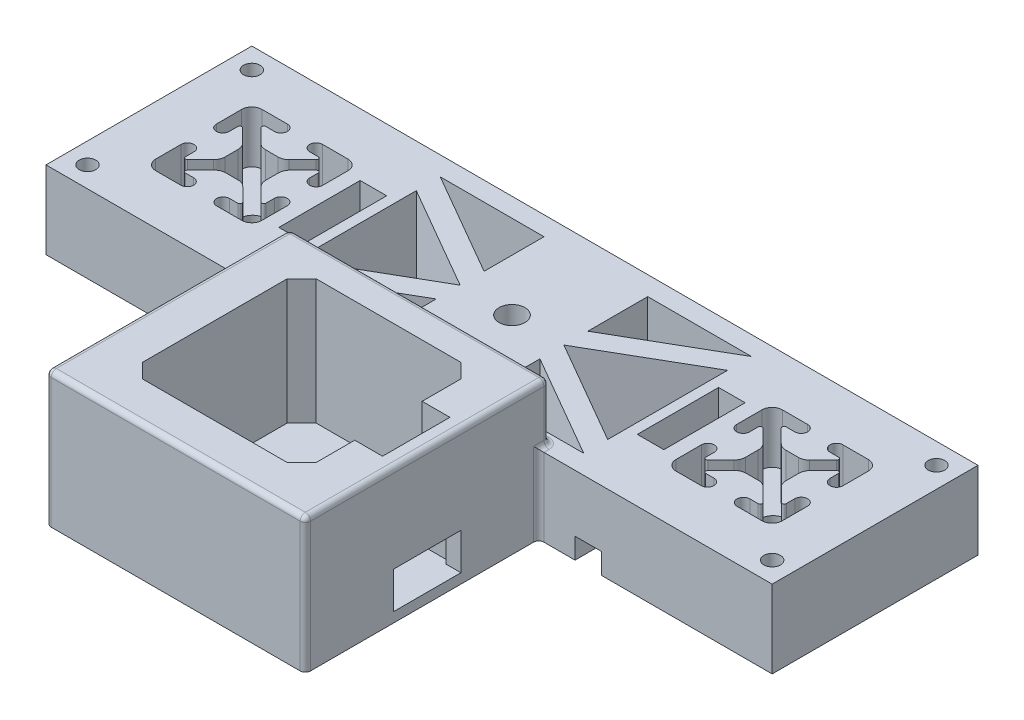
SolidWorks part; units mm, degrees
ref_plane "Front" through (0, 0, 0) normal (0, 0, 1) x (1, 0, 0)
ref_plane "Top" through (0, 0, 0) normal (0, 1, 0) x (1, 0, 0)
ref_plane "Right" through (0, 0, 0) normal (1, 0, 0) x (0, 0, -1)
sketch "Sketch1" plane through (0, 0, 0) normal (0, 1, 0) x (1, 0, 0)
  line L1 (0, 0) -> (177.8, 0)
  line L2 (0, 0) -> (0, 50.4)
  line L3 (0, 50.4) -> (177.8, 50.4)
  line L4 (177.8, 0) -> (177.8, 50.4)
  dimension "D1" = 177.8
  dimension "D2" = 50.4
extrude "Boss-Extrude1" add sketch "Sketch1" along normal blind 6.35
sketch "Sketch2" plane through (0, 6.35, 0) normal (0, 1, 0) x (1, 0, 0)
  line L0 (37.6996, 29.52) -> (37.6996, 35.7372) construction
  line L1 (35.7368, 37.7) -> (29.5196, 37.7) construction
  line L2 (29.5196, 35.56) -> (31.619, 35.56) construction
  line L3 (32.3326, 33.8353) -> (28.9966, 30.504) construction
  line L4 (26.7566, 29.5771) -> (23.643, 29.5771) construction
  line L5 (21.403, 30.504) -> (18.067, 33.8353) construction
  line L6 (18.7806, 35.56) -> (20.88, 35.56) construction
  line L7 (20.88, 37.7) -> (14.6628, 37.7) construction
  line L8 (12.7, 35.7372) -> (12.7, 29.52) construction
  line L9 (14.84, 29.52) -> (14.84, 31.5965) construction
  line L10 (16.5637, 32.3112) -> (19.7659, 29.1135) construction
  line L11 (20.743, 26.7568) -> (20.743, 23.6432) construction
  line L12 (19.7659, 21.2865) -> (16.5637, 18.0888) construction
  line L13 (14.84, 18.8035) -> (14.84, 20.88) construction
  line L14 (12.7, 20.88) -> (12.7, 14.6628) construction
  line L15 (14.6628, 12.7) -> (20.8121, 12.7) construction
  line L16 (20.8121, 14.84) -> (18.7806, 14.84) construction
  line L17 (18.067, 16.5647) -> (21.403, 19.896) construction
  line L18 (23.643, 20.8229) -> (26.7566, 20.8229) construction
  line L19 (28.9966, 19.896) -> (32.3326, 16.5647) construction
  line L20 (31.619, 14.84) -> (29.5875, 14.84) construction
  line L21 (29.5875, 12.7) -> (35.7368, 12.7) construction
  line L22 (37.6996, 14.6628) -> (37.6996, 20.88) construction
  line L23 (35.5596, 20.88) -> (35.5596, 18.8035) construction
  line L24 (33.8359, 18.0888) -> (30.6337, 21.2865) construction
  line L25 (29.6566, 23.6432) -> (29.6566, 26.7568) construction
  line L26 (30.6337, 29.1135) -> (33.8359, 32.3112) construction
  line L27 (35.5596, 31.5965) -> (35.5596, 29.52) construction
  line L28 (0, 50.4) -> (0, 0) construction
  line L29 (177.8, 50.4) -> (0, 50.4) construction
  line L30 (0, 0) -> (177.8, 0) construction
  line L31 (88.9, 50.4) -> (88.9, 0) construction
  line L32 (142.2404, 31.5965) -> (142.2404, 29.52) construction
  line L33 (147.1663, 29.1135) -> (143.9641, 32.3112) construction
  line L34 (148.1434, 23.6432) -> (148.1434, 26.7568) construction
  line L35 (143.9641, 18.0888) -> (147.1663, 21.2865) construction
  line L36 (142.2404, 20.88) -> (142.2404, 18.8035) construction
  line L37 (140.1004, 14.6628) -> (140.1004, 20.88) construction
  line L38 (148.2125, 12.7) -> (142.0632, 12.7) construction
  line L39 (146.181, 14.84) -> (148.2125, 14.84) construction
  line L40 (148.8034, 19.896) -> (145.4674, 16.5647) construction
  line L41 (154.157, 20.8229) -> (151.0434, 20.8229) construction
  line L42 (159.733, 16.5647) -> (156.397, 19.896) construction
  line L43 (156.9879, 14.84) -> (159.0194, 14.84) construction
  line L44 (163.1372, 12.7) -> (156.9879, 12.7) construction
  line L45 (165.1, 20.88) -> (165.1, 14.6628) construction
  line L46 (162.96, 18.8035) -> (162.96, 20.88) construction
  line L47 (158.0341, 21.2865) -> (161.2363, 18.0888) construction
  line L48 (157.057, 26.7568) -> (157.057, 23.6432) construction
  line L49 (161.2363, 32.3112) -> (158.0341, 29.1135) construction
  line L50 (162.96, 29.52) -> (162.96, 31.5965) construction
  line L51 (165.1, 35.7372) -> (165.1, 29.52) construction
  line L52 (156.92, 37.7) -> (163.1372, 37.7) construction
  line L53 (159.0194, 35.56) -> (156.92, 35.56) construction
  line L54 (156.397, 30.504) -> (159.733, 33.8353) construction
  line L55 (151.0434, 29.5771) -> (154.157, 29.5771) construction
  line L56 (145.4674, 33.8353) -> (148.8034, 30.504) construction
  line L57 (148.2804, 35.56) -> (146.181, 35.56) construction
  line L58 (142.0632, 37.7) -> (148.2804, 37.7) construction
  line L59 (140.1004, 29.52) -> (140.1004, 35.7372) construction
  line L60 (38.2076, 29.52) -> (38.2076, 35.7372)
  line L62 (0, 50.4) -> (0, 0)
  line L63 (0, 0) -> (177.8, 0)
  line L64 (177.8, 50.4) -> (177.8, 0)
  line L65 (35.7368, 38.208) -> (29.5196, 38.208)
  line L66 (29.5196, 35.052) -> (31.619, 35.052)
  line L67 (31.9737, 34.1948) -> (28.6376, 30.8635)
  line L68 (26.7566, 30.0851) -> (23.643, 30.0851)
  line L69 (21.762, 30.8635) -> (18.4259, 34.1948)
  line L70 (18.7806, 35.052) -> (20.88, 35.052)
  line L71 (20.88, 38.208) -> (14.6628, 38.208)
  line L72 (12.192, 35.7372) -> (12.192, 29.52)
  line L73 (15.348, 29.52) -> (15.348, 31.5965)
  line L74 (16.2047, 31.9517) -> (19.4069, 28.7541)
  line L75 (20.235, 26.7568) -> (20.235, 23.6432)
  line L76 (19.4069, 21.6459) -> (16.2047, 18.4483)
  line L77 (15.348, 18.8035) -> (15.348, 20.88)
  line L78 (12.192, 20.88) -> (12.192, 14.6628)
  line L79 (14.6628, 12.192) -> (20.8121, 12.192)
  line L80 (20.8121, 15.348) -> (18.7806, 15.348)
  line L81 (18.4259, 16.2052) -> (21.762, 19.5365)
  line L82 (23.643, 20.3149) -> (26.7566, 20.3149)
  line L83 (28.6376, 19.5365) -> (31.9737, 16.2052)
  line L84 (31.619, 15.348) -> (29.5875, 15.348)
  line L85 (29.5875, 12.192) -> (35.7368, 12.192)
  line L86 (38.2076, 14.6628) -> (38.2076, 20.88)
  line L87 (35.0516, 20.88) -> (35.0516, 18.8035)
  line L88 (34.1949, 18.4483) -> (30.9927, 21.6459)
  line L89 (30.1646, 23.6432) -> (30.1646, 26.7568)
  line L90 (30.9927, 28.7541) -> (34.1949, 31.9517)
  line L91 (35.0516, 31.5965) -> (35.0516, 29.52)
  line L92 (142.7484, 31.5965) -> (142.7484, 29.52)
  line L93 (139.5924, 29.52) -> (139.5924, 35.7372)
  line L94 (142.0632, 38.208) -> (148.2804, 38.208)
  line L95 (148.2804, 35.052) -> (146.181, 35.052)
  line L96 (145.8263, 34.1948) -> (149.1624, 30.8635)
  line L97 (151.0434, 30.0851) -> (154.157, 30.0851)
  line L98 (156.038, 30.8635) -> (159.3741, 34.1948)
  line L99 (159.0194, 35.052) -> (156.92, 35.052)
  line L100 (156.92, 38.208) -> (163.1372, 38.208)
  line L101 (165.608, 35.7372) -> (165.608, 29.52)
  line L102 (162.452, 29.52) -> (162.452, 31.5965)
  line L103 (161.5953, 31.9517) -> (158.3931, 28.7541)
  line L104 (157.565, 26.7568) -> (157.565, 23.6432)
  line L105 (158.3931, 21.6459) -> (161.5953, 18.4483)
  line L106 (162.452, 18.8035) -> (162.452, 20.88)
  line L107 (165.608, 20.88) -> (165.608, 14.6628)
  line L108 (163.1372, 12.192) -> (156.9879, 12.192)
  line L109 (156.9879, 15.348) -> (159.0194, 15.348)
  line L110 (159.3741, 16.2052) -> (156.038, 19.5365)
  line L111 (154.157, 20.3149) -> (151.0434, 20.3149)
  line L112 (149.1624, 19.5365) -> (145.8263, 16.2052)
  line L113 (146.181, 15.348) -> (148.2125, 15.348)
  line L114 (148.2125, 12.192) -> (142.0632, 12.192)
  line L115 (139.5924, 14.6628) -> (139.5924, 20.88)
  line L116 (142.7484, 20.88) -> (142.7484, 18.8035)
  line L117 (143.6051, 18.4483) -> (146.8073, 21.6459)
  line L118 (147.6354, 23.6432) -> (147.6354, 26.7568)
  line L119 (146.8073, 28.7541) -> (143.6051, 31.9517)
  line L120 (177.8, 50.4) -> (0, 50.4)
  arc A1 (37.6996, 35.7372) -> (35.7368, 37.7) centre (35.7368, 35.7372) ccw construction
  arc A2 (29.5196, 37.7) -> (29.5196, 35.56) centre (29.5196, 36.63) ccw construction
  arc A3 (31.619, 35.56) -> (32.3326, 33.8353) centre (31.619, 34.55) cw construction
  arc A4 (28.9966, 30.504) -> (26.7566, 29.5771) centre (26.7566, 32.7471) cw construction
  arc A5 (23.643, 29.5771) -> (21.403, 30.504) centre (23.643, 32.7471) cw construction
  arc A6 (18.067, 33.8353) -> (18.7806, 35.56) centre (18.7806, 34.55) cw construction
  arc A7 (20.88, 35.56) -> (20.88, 37.7) centre (20.88, 36.63) ccw construction
  arc A8 (14.6628, 37.7) -> (12.7, 35.7372) centre (14.6628, 35.7372) ccw construction
  arc A9 (12.7, 29.52) -> (14.84, 29.52) centre (13.77, 29.52) ccw construction
  arc A10 (14.84, 31.5965) -> (16.5637, 32.3112) centre (15.85, 31.5965) cw construction
  arc A11 (19.7659, 29.1135) -> (20.743, 26.7568) centre (17.4126, 26.7568) cw construction
  arc A12 (20.743, 23.6432) -> (19.7659, 21.2865) centre (17.4126, 23.6432) cw construction
  arc A13 (16.5637, 18.0888) -> (14.84, 18.8035) centre (15.85, 18.8035) cw construction
  arc A14 (14.84, 20.88) -> (12.7, 20.88) centre (13.77, 20.88) ccw construction
  arc A15 (12.7, 14.6628) -> (14.6628, 12.7) centre (14.6628, 14.6628) ccw construction
  arc A16 (20.8121, 12.7) -> (20.8121, 14.84) centre (20.8121, 13.77) ccw construction
  arc A17 (18.7806, 14.84) -> (18.067, 16.5647) centre (18.7806, 15.85) cw construction
  arc A18 (21.403, 19.896) -> (23.643, 20.8229) centre (23.643, 17.6529) cw construction
  arc A19 (26.7566, 20.8229) -> (28.9966, 19.896) centre (26.7566, 17.6529) cw construction
  arc A20 (32.3326, 16.5647) -> (31.619, 14.84) centre (31.619, 15.85) cw construction
  arc A21 (29.5875, 14.84) -> (29.5875, 12.7) centre (29.5875, 13.77) ccw construction
  arc A22 (35.7368, 12.7) -> (37.6996, 14.6628) centre (35.7368, 14.6628) ccw construction
  arc A23 (37.6996, 20.88) -> (35.5596, 20.88) centre (36.6296, 20.88) ccw construction
  arc A24 (35.5596, 18.8035) -> (33.8359, 18.0888) centre (34.5496, 18.8035) cw construction
  arc A25 (30.6337, 21.2865) -> (29.6566, 23.6432) centre (32.987, 23.6432) cw construction
  arc A26 (29.6566, 26.7568) -> (30.6337, 29.1135) centre (32.987, 26.7568) cw construction
  arc A27 (33.8359, 32.3112) -> (35.5596, 31.5965) centre (34.5496, 31.5965) cw construction
  arc A28 (35.5596, 29.52) -> (37.6996, 29.52) centre (36.6296, 29.52) ccw construction
  arc A29 (142.2404, 29.52) -> (140.1004, 29.52) centre (141.1704, 29.52) cw construction
  arc A30 (143.9641, 32.3112) -> (142.2404, 31.5965) centre (143.2504, 31.5965) ccw construction
  arc A31 (148.1434, 26.7568) -> (147.1663, 29.1135) centre (144.813, 26.7568) ccw construction
  arc A32 (147.1663, 21.2865) -> (148.1434, 23.6432) centre (144.813, 23.6432) ccw construction
  arc A33 (142.2404, 18.8035) -> (143.9641, 18.0888) centre (143.2504, 18.8035) ccw construction
  arc A34 (140.1004, 20.88) -> (142.2404, 20.88) centre (141.1704, 20.88) cw construction
  arc A35 (142.0632, 12.7) -> (140.1004, 14.6628) centre (142.0632, 14.6628) cw construction
  arc A36 (148.2125, 14.84) -> (148.2125, 12.7) centre (148.2125, 13.77) cw construction
  arc A37 (145.4674, 16.5647) -> (146.181, 14.84) centre (146.181, 15.85) ccw construction
  arc A38 (151.0434, 20.8229) -> (148.8034, 19.896) centre (151.0434, 17.6529) ccw construction
  arc A39 (156.397, 19.896) -> (154.157, 20.8229) centre (154.157, 17.6529) ccw construction
  arc A40 (159.0194, 14.84) -> (159.733, 16.5647) centre (159.0194, 15.85) ccw construction
  arc A41 (156.9879, 12.7) -> (156.9879, 14.84) centre (156.9879, 13.77) cw construction
  arc A42 (165.1, 14.6628) -> (163.1372, 12.7) centre (163.1372, 14.6628) cw construction
  arc A43 (162.96, 20.88) -> (165.1, 20.88) centre (164.03, 20.88) cw construction
  arc A44 (161.2363, 18.0888) -> (162.96, 18.8035) centre (161.95, 18.8035) ccw construction
  arc A45 (157.057, 23.6432) -> (158.0341, 21.2865) centre (160.3874, 23.6432) ccw construction
  arc A46 (158.0341, 29.1135) -> (157.057, 26.7568) centre (160.3874, 26.7568) ccw construction
  arc A47 (162.96, 31.5965) -> (161.2363, 32.3112) centre (161.95, 31.5965) ccw construction
  arc A48 (165.1, 29.52) -> (162.96, 29.52) centre (164.03, 29.52) cw construction
  arc A49 (163.1372, 37.7) -> (165.1, 35.7372) centre (163.1372, 35.7372) cw construction
  arc A50 (156.92, 35.56) -> (156.92, 37.7) centre (156.92, 36.63) cw construction
  arc A51 (159.733, 33.8353) -> (159.0194, 35.56) centre (159.0194, 34.55) ccw construction
  arc A52 (154.157, 29.5771) -> (156.397, 30.504) centre (154.157, 32.7471) ccw construction
  arc A53 (148.8034, 30.504) -> (151.0434, 29.5771) centre (151.0434, 32.7471) ccw construction
  arc A54 (146.181, 35.56) -> (145.4674, 33.8353) centre (146.181, 34.55) ccw construction
  arc A55 (148.2804, 37.7) -> (148.2804, 35.56) centre (148.2804, 36.63) cw construction
  arc A56 (140.1004, 35.7372) -> (142.0632, 37.7) centre (142.0632, 35.7372) cw construction
  arc A58 (38.2076, 35.7372) -> (35.7368, 38.208) centre (35.7368, 35.7372) ccw
  arc A59 (29.5196, 38.208) -> (29.5196, 35.052) centre (29.5196, 36.63) ccw
  arc A60 (31.619, 35.052) -> (31.9737, 34.1948) centre (31.619, 34.55) cw
  arc A61 (28.6376, 30.8635) -> (26.7566, 30.0851) centre (26.7566, 32.7471) cw
  arc A62 (23.643, 30.0851) -> (21.762, 30.8635) centre (23.643, 32.7471) cw
  arc A63 (18.4259, 34.1948) -> (18.7806, 35.052) centre (18.7806, 34.55) cw
  arc A64 (20.88, 35.052) -> (20.88, 38.208) centre (20.88, 36.63) ccw
  arc A65 (14.6628, 38.208) -> (12.192, 35.7372) centre (14.6628, 35.7372) ccw
  arc A66 (12.192, 29.52) -> (15.348, 29.52) centre (13.77, 29.52) ccw
  arc A67 (15.348, 31.5965) -> (16.2047, 31.9517) centre (15.85, 31.5965) cw
  arc A68 (19.4069, 28.7541) -> (20.235, 26.7568) centre (17.4126, 26.7568) cw
  arc A69 (20.235, 23.6432) -> (19.4069, 21.6459) centre (17.4126, 23.6432) cw
  arc A70 (16.2047, 18.4483) -> (15.348, 18.8035) centre (15.85, 18.8035) cw
  arc A71 (15.348, 20.88) -> (12.192, 20.88) centre (13.77, 20.88) ccw
  arc A72 (12.192, 14.6628) -> (14.6628, 12.192) centre (14.6628, 14.6628) ccw
  arc A73 (20.8121, 12.192) -> (20.8121, 15.348) centre (20.8121, 13.77) ccw
  arc A74 (18.7806, 15.348) -> (18.4259, 16.2052) centre (18.7806, 15.85) cw
  arc A75 (21.762, 19.5365) -> (23.643, 20.3149) centre (23.643, 17.6529) cw
  arc A76 (26.7566, 20.3149) -> (28.6376, 19.5365) centre (26.7566, 17.6529) cw
  arc A77 (31.9737, 16.2052) -> (31.619, 15.348) centre (31.619, 15.85) cw
  arc A78 (29.5875, 15.348) -> (29.5875, 12.192) centre (29.5875, 13.77) ccw
  arc A79 (35.7368, 12.192) -> (38.2076, 14.6628) centre (35.7368, 14.6628) ccw
  arc A80 (38.2076, 20.88) -> (35.0516, 20.88) centre (36.6296, 20.88) ccw
  arc A81 (35.0516, 18.8035) -> (34.1949, 18.4483) centre (34.5496, 18.8035) cw
  arc A82 (30.9927, 21.6459) -> (30.1646, 23.6432) centre (32.987, 23.6432) cw
  arc A83 (30.1646, 26.7568) -> (30.9927, 28.7541) centre (32.987, 26.7568) cw
  arc A84 (34.1949, 31.9517) -> (35.0516, 31.5965) centre (34.5496, 31.5965) cw
  arc A85 (35.0516, 29.52) -> (38.2076, 29.52) centre (36.6296, 29.52) ccw
  arc A86 (142.7484, 29.52) -> (139.5924, 29.52) centre (141.1704, 29.52) cw
  arc A87 (139.5924, 35.7372) -> (142.0632, 38.208) centre (142.0632, 35.7372) cw
  arc A88 (148.2804, 38.208) -> (148.2804, 35.052) centre (148.2804, 36.63) cw
  arc A89 (146.181, 35.052) -> (145.8263, 34.1948) centre (146.181, 34.55) ccw
  arc A90 (149.1624, 30.8635) -> (151.0434, 30.0851) centre (151.0434, 32.7471) ccw
  arc A91 (154.157, 30.0851) -> (156.038, 30.8635) centre (154.157, 32.7471) ccw
  arc A92 (159.3741, 34.1948) -> (159.0194, 35.052) centre (159.0194, 34.55) ccw
  arc A93 (156.92, 35.052) -> (156.92, 38.208) centre (156.92, 36.63) cw
  arc A94 (163.1372, 38.208) -> (165.608, 35.7372) centre (163.1372, 35.7372) cw
  arc A95 (165.608, 29.52) -> (162.452, 29.52) centre (164.03, 29.52) cw
  arc A96 (162.452, 31.5965) -> (161.5953, 31.9517) centre (161.95, 31.5965) ccw
  arc A97 (158.3931, 28.7541) -> (157.565, 26.7568) centre (160.3874, 26.7568) ccw
  arc A98 (157.565, 23.6432) -> (158.3931, 21.6459) centre (160.3874, 23.6432) ccw
  arc A99 (161.5953, 18.4483) -> (162.452, 18.8035) centre (161.95, 18.8035) ccw
  arc A100 (162.452, 20.88) -> (165.608, 20.88) centre (164.03, 20.88) cw
  arc A101 (165.608, 14.6628) -> (163.1372, 12.192) centre (163.1372, 14.6628) cw
  arc A102 (156.9879, 12.192) -> (156.9879, 15.348) centre (156.9879, 13.77) cw
  arc A103 (159.0194, 15.348) -> (159.3741, 16.2052) centre (159.0194, 15.85) ccw
  arc A104 (156.038, 19.5365) -> (154.157, 20.3149) centre (154.157, 17.6529) ccw
  arc A105 (151.0434, 20.3149) -> (149.1624, 19.5365) centre (151.0434, 17.6529) ccw
  arc A106 (145.8263, 16.2052) -> (146.181, 15.348) centre (146.181, 15.85) ccw
  arc A107 (148.2125, 15.348) -> (148.2125, 12.192) centre (148.2125, 13.77) cw
  arc A108 (142.0632, 12.192) -> (139.5924, 14.6628) centre (142.0632, 14.6628) cw
  arc A109 (139.5924, 20.88) -> (142.7484, 20.88) centre (141.1704, 20.88) cw
  arc A110 (142.7484, 18.8035) -> (143.6051, 18.4483) centre (143.2504, 18.8035) ccw
  arc A111 (146.8073, 21.6459) -> (147.6354, 23.6432) centre (144.813, 23.6432) ccw
  arc A112 (147.6354, 26.7568) -> (146.8073, 28.7541) centre (144.813, 26.7568) ccw
  arc A113 (143.6051, 31.9517) -> (142.7484, 31.5965) centre (143.2504, 31.5965) ccw
  dimension "D2" = 1.07
  dimension "D3" = 3.17
  dimension "D4" = 3.3305
  dimension "D8" = 1.9628
  dimension "D9" = 1.01
  dimension "D5" = 12.7
  dimension "D6" = 12.7
  dimension "D7" = 12.7
  dimension "D10" = 16.5637
  dimension "D12" = 0.508
  dimension "D13" = 0.508
extrude "Boss-Extrude2" add sketch "Sketch2" along normal blind 12.7
sketch "Sketch3" plane through (0, 19.05, 0) normal (0, 1, 0) x (1, 0, 0)
  line L0 (177.8, 50.4) -> (0, 50.4) construction
  line L1 (0, 50.4) -> (0, 0) construction
  circle A0 centre (88.9, 25.2) radius 3.175
  point P4 (88.9, 50.4)
  point P7 (0, 25.2)
  dimension "D1" = 6.35
extrude "Cut-Extrude1" cut sketch "Sketch3" against normal through all
sketch "Sketch4" plane through (0, 19.05, 0) normal (0, 1, 0) x (1, 0, 0)
  line L0 (50.8, 45.7306) -> (76.2, 45.7306)
  line L1 (76.2, 45.7306) -> (76.2, 31.0659)
  line L2 (76.2, 31.0659) -> (50.8, 45.7306)
  line L3 (76.2, 19.3341) -> (76.2, 4.6694)
  line L4 (76.2, 4.6694) -> (50.8, 4.6694)
  line L5 (50.8, 4.6694) -> (76.2, 19.3341)
  line L6 (50.8, 39.8647) -> (50.8, 10.5353)
  line L7 (50.8, 10.5353) -> (76.2, 25.2)
  line L8 (76.2, 25.2) -> (50.8, 39.8647)
  line L9 (0, 50.4) -> (0, 0) construction
  line L10 (88.9, 50.4) -> (88.9, 0) construction
  line L11 (177.8, 50.4) -> (0, 50.4) construction
  line L12 (0, 0) -> (177.8, 0) construction
  line L13 (101.6, 25.2) -> (127, 39.8647)
  line L14 (127, 10.5353) -> (101.6, 25.2)
  line L15 (127, 39.8647) -> (127, 10.5353)
  line L16 (127, 4.6694) -> (101.6, 19.3341)
  line L17 (101.6, 4.6694) -> (127, 4.6694)
  line L18 (101.6, 19.3341) -> (101.6, 4.6694)
  line L19 (101.6, 31.0659) -> (127, 45.7306)
  line L20 (101.6, 45.7306) -> (101.6, 31.0659)
  line L21 (127, 45.7306) -> (101.6, 45.7306)
  point P18 (88.9, 25.2)
  dimension "D1" = 25.4
  dimension "D2" = 25.4
  dimension "D3" = 50.8
  dimension "D4" = 5.08
  dimension "D5" = 5.08
  dimension "D7" = 60
extrude "Cut-Extrude2" cut sketch "Sketch4" against normal through all
sketch "Sketch5" plane through (0, 19.05, 0) normal (0, 1, 0) x (1, 0, 0)
  line L0 (0, 50.4) -> (0, 0) construction
  line L1 (41.7636, 35.15) -> (48.2636, 35.15)
  line L2 (41.7636, 35.15) -> (41.7636, 15.25)
  line L3 (41.7636, 15.25) -> (48.2636, 15.25)
  line L4 (48.2636, 35.15) -> (48.2636, 15.25)
  line L5 (38.2076, 29.52) -> (38.2076, 35.7372) construction
  point P6 (0, 25.2)
  point P7 (48.2636, 25.2)
  dimension "D1" = 6.5
  dimension "D2" = 19.9
  dimension "D3" = 3.556
extrude "Cut-Extrude3" cut sketch "Sketch5" against normal blind 10.2
sketch "Sketch6" plane through (0, 8.85, 0) normal (0, 1, 0) x (1, 0, 0)
  line L0 (48.2636, 15.25) -> (48.2636, 35.15) construction
  line L1 (41.7636, 35.15) -> (48.2636, 35.15)
  line L2 (41.7636, 35.15) -> (41.7636, 30.578)
  line L3 (41.7636, 30.578) -> (48.2636, 30.578)
  line L4 (48.2636, 35.15) -> (48.2636, 30.578)
  line L5 (41.7636, 35.15) -> (41.7636, 15.25) construction
  line L6 (48.2636, 15.25) -> (48.2636, 35.15) construction
  line L7 (41.7636, 27.486) -> (48.2636, 27.486)
  line L8 (41.7636, 27.486) -> (41.7636, 22.914)
  line L9 (41.7636, 22.914) -> (48.2636, 22.914)
  line L10 (48.2636, 27.486) -> (48.2636, 22.914)
  line L12 (41.7636, 15.25) -> (48.2636, 15.25)
  line L13 (41.7636, 15.25) -> (41.7636, 19.822)
  line L14 (41.7636, 19.822) -> (48.2636, 19.822)
  line L15 (48.2636, 15.25) -> (48.2636, 19.822)
  line L16 (41.7636, 25.2) -> (0, 25.2) construction
  line L17 (0, 50.4) -> (0, 0) construction
  dimension "D1" = 4.572
extrude "Cut-Extrude4" cut sketch "Sketch6" against normal through all
ref_plane "Plane1" through (88.9, 0, 0) normal (-1, 0, 0) x (0, 0, 1)
mirror "Mirror1" about plane through (88.9, 0, 0) normal (-1, 0, 0) of "Cut-Extrude4", "Cut-Extrude3"
sketch "Sketch7" plane through (0, 6.35, 0) normal (0, 1, 0) x (1, 0, 0)
  line L0 (26.7566, 30.0851) -> (23.643, 30.0851) construction
  line L1 (30.1646, 23.6432) -> (30.1646, 26.7568) construction
  circle A0 centre (25.3386, 25.2591) radius 2.921
  dimension "D1" = 5.842
  dimension "D2" = 4.826
  dimension "D3" = 4.826
extrude "Cut-Extrude5" cut sketch "Sketch7" against normal through all both and the other way through all
sketch "Sketch8" plane through (0, 6.35, 0) normal (0, 1, 0) x (1, 0, 0)
  line L0 (154.157, 30.0851) -> (151.0434, 30.0851) construction
  line L1 (157.565, 23.6432) -> (157.565, 26.7568) construction
  circle A0 centre (152.739, 25.2591) radius 2.921
  dimension "D1" = 5.842
  dimension "D2" = 4.826
  dimension "D3" = 4.826
extrude "Cut-Extrude6" cut sketch "Sketch8" against normal through all both and the other way through all
chamfer "Chamfer2" distance 3.302 angle 45 1 edges at (152.739, 0, -22.3381)
chamfer "Chamfer3" distance 3.302 angle 45 1 edges at (25.3386, 0, -22.3381)
sketch "Sketch9" plane through (0, 0, 0) normal (0, 1, 0) x (1, 0, 0)
  line L0 (120.65, 0) -> (120.65, -57.15)
  line L3 (0, 0) -> (177.8, 0) construction
  line L8 (57.15, -57.15) -> (120.65, -57.15)
  line L13 (57.15, 0) -> (57.15, -57.15)
  line L15 (57.15, 0) -> (57.15, 2.54)
  line L16 (57.15, 2.54) -> (120.65, 2.54)
  line L17 (120.65, 0) -> (120.65, 2.54)
  dimension "D1" = 57.15
  dimension "D2" = 63.5
  dimension "D3" = 2.54
sketch "Sketch11" plane through (0, 0, 0) normal (0, 1, 0) x (1, 0, 0)
  line L0 (0, 0) -> (177.8, 0) construction
  line L2 (41.7636, 15.25) -> (41.7636, 0)
  line L3 (41.7636, 0) -> (48.2636, 0)
  line L4 (48.2636, 15.25) -> (48.2636, 0)
  line L5 (48.2636, 15.25) -> (48.2636, 35.15) construction
  line L6 (177.8, 50.4) -> (0, 50.4) construction
  line L8 (41.7636, 35.15) -> (41.7636, 50.4)
  line L9 (41.7636, 50.4) -> (48.2636, 50.4)
  line L10 (48.2636, 35.15) -> (48.2636, 50.4)
  line L11 (41.7636, 35.15) -> (41.7636, 15.25)
  line L12 (48.2636, 35.15) -> (48.2636, 15.25)
  line L13 (88.9, 50.4) -> (88.9, 0) construction
  line L14 (136.0364, 0) -> (129.5364, 0)
  line L15 (136.0364, 50.4) -> (129.5364, 50.4)
  line L16 (129.5364, 15.25) -> (129.5364, 0)
  line L17 (136.0364, 15.25) -> (136.0364, 0)
  line L18 (129.5364, 35.15) -> (129.5364, 15.25)
  line L19 (136.0364, 35.15) -> (136.0364, 15.25)
  line L20 (129.5364, 35.15) -> (129.5364, 50.4)
  line L21 (136.0364, 35.15) -> (136.0364, 50.4)
extrude "Cut-Extrude8" cut sketch "Sketch11" along normal blind 5.08
extrude "Boss-Extrude4" add sketch "Sketch9" along normal blind 33.02
sketch "Sketch12" plane through (0, 33.02, 0) normal (0, 1, 0) x (1, 0, 0)
  line L0 (71.1855, -5.05) -> (106.6145, -5.05)
  line L1 (106.6145, -5.05) -> (110.15, -8.5855)
  line L2 (110.15, -8.5855) -> (110.15, -18.05)
  line L3 (110.15, -44.0145) -> (106.6145, -47.55)
  line L4 (106.6145, -47.55) -> (71.1855, -47.55)
  line L5 (71.1855, -47.55) -> (67.65, -44.0145)
  line L6 (67.65, -44.0145) -> (67.65, -8.5855)
  line L7 (67.65, -8.5855) -> (71.1855, -5.05)
  line L8 (57.15, -57.15) -> (120.65, -57.15) construction
  line L10 (110.15, -34.55) -> (110.15, -44.0145)
  line L11 (110.15, -18.05) -> (116.95, -18.05)
  line L13 (110.15, -34.55) -> (116.95, -34.55)
  line L14 (116.95, -18.05) -> (116.95, -34.55)
  point P10 (88.9, -57.15)
  point P11 (88.9, -47.55)
  point P15 (67.65, -26.3)
  point P21 (116.95, -26.3)
  dimension "D1" = 5
  dimension "D2" = 42.5
  dimension "D3" = 135
  dimension "D4" = 135
  dimension "D5" = 135
  dimension "D6" = 42.5
  dimension "D7" = 16.5
  dimension "D8" = 6.8
extrude "Cut-Extrude9" cut sketch "Sketch12" against normal blind 30.6
sketch "Sketch13" plane through (120.65, 0, 0) normal (1, 0, 0) x (0, 0, -1)
  line L0 (-57.15, 33.02) -> (2.54, 33.02) construction
  line L1 (-35.555, 11.42) -> (-19.055, 11.42)
  line L2 (-35.555, 11.42) -> (-35.555, 2.42)
  line L3 (-35.555, 2.42) -> (-19.055, 2.42)
  line L4 (-19.055, 11.42) -> (-19.055, 2.42)
  point P6 (-27.305, 33.02)
  point P7 (-27.305, 11.42)
  dimension "D1" = 16.5
  dimension "D2" = 9
  dimension "D3" = 30.6
extrude "Cut-Extrude10" cut sketch "Sketch13" against normal blind 30.6
fillet "Fillet1" radius 1.27 13 edges at (120.65, 19.05, -1.27) (57.15, 19.05, -1.27) (120.65, 26.035, -2.54) (57.15, 26.035, -2.54) (88.9, 19.05, -2.54) (57.15, 9.525, 0) (120.65, 9.525, 0) (120.65, 33.02, 27.305) (120.65, 16.51, 57.15) (88.9, 33.02, 57.15) (57.15, 33.02, 27.305) (57.15, 16.51, 57.15) (88.9, 33.02, -2.54)
sketch "Sketch14" plane through (0, 2.42, 0) normal (0, 1, 0) x (1, 0, 0)
  line L0 (88.9, -5.05) -> (88.9, -47.55) construction
  line L1 (106.6145, -5.05) -> (71.1855, -5.05) construction
  line L2 (71.1855, -47.55) -> (106.6145, -47.55) construction
  circle A0 centre (88.9, -26.3) radius 2.921
  dimension "D1" = 5.842
extrude "Cut-Extrude11" cut sketch "Sketch14" against normal through all
sketch "Sketch15" plane through (0, 0, 0) normal (0, 1, 0) x (1, 0, 0)
  circle A0 centre (88.9, 25.2) radius 7.62
  dimension "D1" = 15.24
extrude "Cut-Extrude12" cut sketch "Sketch15" along normal blind 8.128
sketch "Sketch16" plane through (0, 19.05, 0) normal (0, 1, 0) x (1, 0, 0)
  line L0 (88.9, 50.4) -> (88.9, -47.55) construction
  line L1 (177.8, 50.4) -> (0, 50.4) construction
  line L2 (71.1855, -47.55) -> (106.6145, -47.55) construction
  line L3 (0, 25.2) -> (177.8, 25.2) construction
  line L4 (0, 50.4) -> (0, 0) construction
  line L5 (177.8, 0) -> (177.8, 50.4) construction
  circle A0 centre (5.08, 45.32) radius 2.032
  circle A1 centre (5.08, 5.08) radius 2.032
  circle A2 centre (172.72, 5.08) radius 2.032
  circle A3 centre (172.72, 45.32) radius 2.032
  dimension "D1" = 4.064
  dimension "D3" = 5.08
  dimension "D2" = 5.08
extrude "Cut-Extrude13" cut sketch "Sketch16" against normal through all
